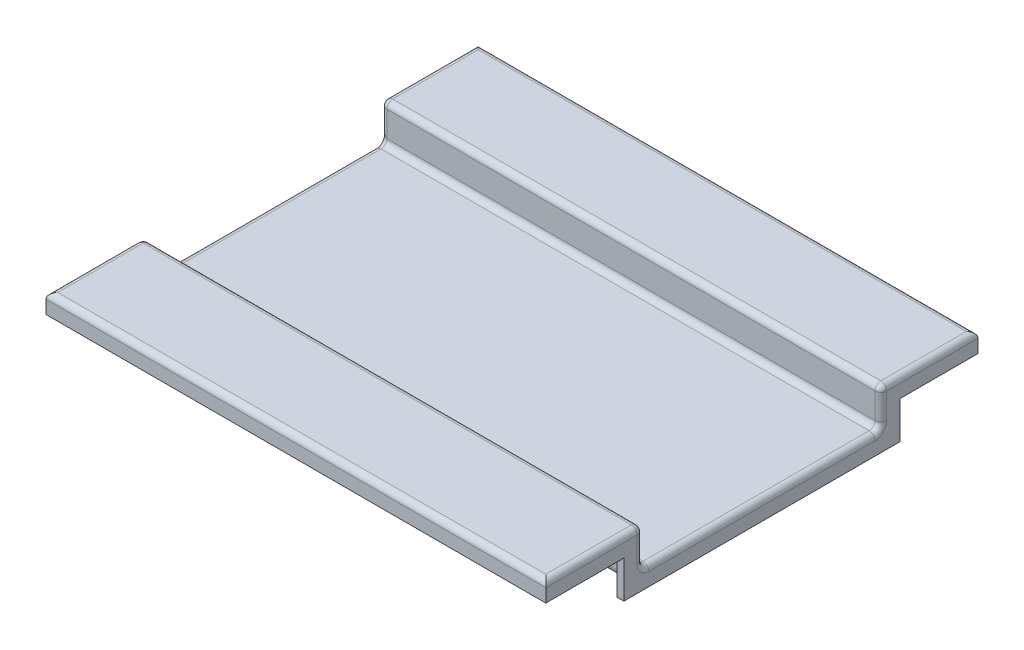
SolidWorks part; units mm, degrees
ref_plane "Alzado" through (0, 0, 0) normal (0, 0, 1) x (1, 0, 0)
ref_plane "Planta" through (0, 0, 0) normal (0, 1, 0) x (1, 0, 0)
ref_plane "Vista lateral" through (0, 0, 0) normal (1, 0, 0) x (0, 0, -1)
sketch "Croquis2" plane through (0, 0, 0) normal (0, 1, 0) x (1, 0, 0)
  line L1 (0, 0) -> (170, 0)
  line L2 (0, 0) -> (0, 147)
  line L3 (0, 147) -> (170, 147)
  line L4 (170, 0) -> (170, 147)
  dimension "D1" = 170
  dimension "D2" = 147
extrude "Saliente-Extruir1" add sketch "Croquis2" along normal blind 19.2
sketch "Croquis5" plane through (0, 19.2, 0) normal (0, 1, 0) x (1, 0, 0)
  line L0 (0, 147) -> (0, 0) construction
  line L1 (0, 33.05) -> (170, 33.05)
  line L2 (0, 33.05) -> (0, 113.95)
  line L3 (0, 113.95) -> (170, 113.95)
  line L4 (170, 33.05) -> (170, 113.95)
  line L5 (170, 0) -> (170, 147) construction
  line L6 (0, 73.5) -> (170, 73.5) construction
  point P10 (0, 73.5)
  dimension "D1" = 80.9
extrude "Cortar-Extruir1" cut sketch "Croquis5" against normal blind 12.7
sketch "Croquis6" plane through (170, 0, 0) normal (1, 0, 0) x (0, 0, -1)
  line L0 (73.5, 0) -> (73.5, 6.5) construction
  line L1 (0, 0) -> (26.55, 0)
  line L2 (0, 0) -> (0, 12.7)
  line L3 (0, 12.7) -> (26.55, 12.7)
  line L4 (26.55, 0) -> (26.55, 12.7)
  line L5 (0, 0) -> (147, 0) construction
  line L6 (33.05, 6.5) -> (113.95, 6.5) construction
  line L7 (0, 19.2) -> (33.05, 19.2) construction
  line L8 (33.05, 6.5) -> (33.05, 19.2) construction
  line L9 (147, 12.7) -> (120.45, 12.7)
  line L10 (120.45, 0) -> (120.45, 12.7)
  line L11 (147, 0) -> (120.45, 0)
  line L12 (147, 0) -> (147, 12.7)
  dimension "D1" = 6.5
  dimension "D2" = 6.5
extrude "Cortar-Extruir2" cut sketch "Croquis6" against normal through all
sketch "Croquis7" plane through (0, 12.7, 0) normal (0, -1, 0) x (1, 0, 0)
  line L0 (0, -73.5) -> (170, -73.5) construction
  line L1 (0, -120.45) -> (0, -26.55) construction
  line L2 (170, -26.55) -> (170, -120.45) construction
  line L3 (85, 0) -> (85, -147) construction
  line L4 (2.3, -120.45) -> (167.7, -120.45)
  line L5 (2.3, -120.45) -> (2.3, -144.7)
  line L6 (2.3, -144.7) -> (167.7, -144.7)
  line L7 (167.7, -120.45) -> (167.7, -144.7)
  line L8 (0, 0) -> (170, 0) construction
  line L9 (0, -147) -> (170, -147) construction
  line L10 (0, -26.55) -> (0, 0) construction
  line L11 (170, -26.55) -> (170, 0) construction
  line L12 (0, -120.45) -> (170, -120.45) construction
  line L13 (2.3, -2.3) -> (167.7, -2.3)
  line L14 (167.7, -26.55) -> (167.7, -2.3)
  line L15 (2.3, -26.55) -> (167.7, -26.55)
  line L16 (2.3, -26.55) -> (2.3, -2.3)
  point P21 (2.3, -2.3)
  dimension "D1" = 2.3
  dimension "D2" = 2.3
  dimension "D3" = 2.3
extrude "Cortar-Extruir4" cut sketch "Croquis7" against normal blind 3
sketch "Croquis8" plane through (0, 0, -26.55) normal (0, 0, 1) x (1, 0, 0)
  line L0 (0, 0) -> (170, 0) construction
  line L1 (2.3, 15.7) -> (167.7, 15.7)
  line L2 (2.3, 15.7) -> (2.3, 0)
  line L3 (2.3, 0) -> (167.7, 0)
  line L4 (167.7, 15.7) -> (167.7, 0)
  point P7 (167.7, 15.7)
extrude "Cortar-Extruir6" cut sketch "Croquis8" against normal blind 3
sketch "Croquis9" plane through (0, 0, -120.45) normal (0, 0, -1) x (-1, 0, 0)
  line L0 (0, 0) -> (-170, 0) construction
  line L1 (-167.7, 15.7) -> (-2.3, 15.7)
  line L2 (-167.7, 15.7) -> (-167.7, 0)
  line L3 (-167.7, 0) -> (-2.3, 0)
  line L4 (-2.3, 15.7) -> (-2.3, 0)
  line L5 (-2.3, 15.7) -> (-2.3, 12.7) construction
  point P7 (-2.3, 15.7)
extrude "Cortar-Extruir7" cut sketch "Croquis9" against normal blind 3
sketch "Croquis10" plane through (0, 0, 0) normal (0, -1, 0) x (1, 0, 0)
  line L1 (2.3, -29.55) -> (167.7, -29.55)
  line L2 (2.3, -29.55) -> (2.3, -117.45)
  line L3 (2.3, -117.45) -> (167.7, -117.45)
  line L4 (167.7, -29.55) -> (167.7, -117.45)
extrude "Cortar-Extruir8" cut sketch "Croquis10" against normal blind 3
sketch "Croquis15" plane through (0, 3, 0) normal (0, -1, 0) x (1, 0, 0)
  line L0 (2.3, -73.5) -> (167.7, -73.5) construction
  line L1 (2.3, -29.55) -> (2.3, -117.45) construction
  line L2 (167.7, -117.45) -> (167.7, -29.55) construction
  line L3 (85, -29.55) -> (85, -117.45) construction
  line L4 (167.7, -29.55) -> (2.3, -29.55) construction
  line L5 (2.3, -117.45) -> (167.7, -117.45) construction
  line L7 (80, -40.7109) -> (90, -40.7109)
  line L8 (80, -40.7109) -> (80, -59.4109)
  line L10 (90, -40.7109) -> (90, -59.4109)
  line L12 (90, -106.2891) -> (90, -87.5891)
  line L13 (80, -106.2891) -> (90, -106.2891)
  line L14 (80, -106.2891) -> (80, -87.5891)
  line L15 (70.9109, -78.5) -> (52.2109, -78.5)
  line L16 (99.0891, -68.5) -> (117.7891, -68.5)
  line L18 (99.0891, -78.5) -> (117.7891, -78.5)
  line L19 (117.7891, -68.5) -> (117.7891, -78.5)
  line L20 (52.2109, -68.5) -> (52.2109, -78.5)
  line L21 (70.9109, -68.5) -> (52.2109, -68.5)
  arc A0 (80, -59.4109) -> (70.9109, -68.5) centre (85, -73.5) ccw
  arc A1 (70.9109, -78.5) -> (80, -87.5891) centre (85, -73.5) ccw
  arc A2 (90, -87.5891) -> (99.0891, -78.5) centre (85, -73.5) ccw
  arc A3 (99.0891, -68.5) -> (90, -59.4109) centre (85, -73.5) ccw
  point P20 (85, -40.7109)
  point P29 (117.7891, -73.5)
  dimension "D1" = 29.9
  dimension "D2" = 18.7
  dimension "D3" = 10
  dimension "D4" = 18.7
  dimension "D5" = 18.7
  dimension "D6" = 18.7
  dimension "D7" = 10
  dimension "D8" = 18.7
  dimension "D9" = 18.7
extrude "Saliente-Extruir4" add sketch "Croquis15" along normal blind 18.7
sketch "Croquis20" plane through (90, 0, 0) normal (1, 0, 0) x (0, 0, -1)
  line L0 (59.4109, -15.7) -> (40.7109, 3)
  line L1 (40.7109, 3) -> (40.7109, -15.7)
  line L2 (40.7109, -15.7) -> (59.4109, -15.7)
extrude "Cortar-Extruir11" cut sketch "Croquis20" against normal up to next
sketch "Croquis21" plane through (90, 0, 0) normal (1, 0, 0) x (0, 0, -1)
  line L0 (87.5891, -15.7) -> (106.2891, 3)
  line L1 (106.2891, 3) -> (106.2891, -15.7)
  line L2 (87.5891, -15.7) -> (106.2891, -15.7)
extrude "Cortar-Extruir13" cut sketch "Croquis21" against normal up to next
sketch "Croquis22" plane through (0, 0, -78.5) normal (0, 0, -1) x (-1, 0, 0)
  line L0 (-99.0891, -15.7) -> (-117.7891, 3)
  line L1 (-117.7891, 3) -> (-117.7891, -15.7)
  line L2 (-117.7891, -15.7) -> (-99.0891, -15.7)
  line L3 (-70.9109, -15.7) -> (-52.2109, -15.7)
  line L4 (-52.2109, -15.7) -> (-52.2109, 3)
  line L5 (-52.2109, 3) -> (-70.9109, -15.7)
extrude "Cortar-Extruir14" cut sketch "Croquis22" against normal up to next
sketch "Croquis23" plane through (0, -15.7, 0) normal (0, -1, 0) x (1, 0, 0)
  line L0 (85, -59.4109) -> (85, -87.5891) construction
  line L1 (80, -59.4109) -> (90, -59.4109) construction
  line L2 (80, -87.5891) -> (90, -87.5891) construction
  line L3 (85, -59.4109) -> (85, -40.7109) construction
  line L4 (90, -40.7109) -> (80, -40.7109) construction
  line L5 (85, -87.5891) -> (85, -106.2891) construction
  line L6 (80, -106.2891) -> (90, -106.2891) construction
  line L7 (52.2109, -73.5) -> (117.7891, -73.5) construction
  line L8 (52.2109, -68.5) -> (52.2109, -78.5) construction
  line L9 (117.7891, -78.5) -> (117.7891, -68.5) construction
  line L10 (70.9109, -68.5) -> (70.9109, -78.5) construction
  line L11 (52.2109, -70.7) -> (70.0691, -70.7)
  line L12 (52.2109, -70.7) -> (52.2109, -76.3)
  line L13 (52.2109, -76.3) -> (70.0691, -76.3)
  line L14 (70.0691, -70.7) -> (70.0691, -76.3)
  line L15 (117.7891, -76.3) -> (99.9309, -76.3)
  line L16 (99.9309, -70.7) -> (99.9309, -76.3)
  line L17 (117.7891, -70.7) -> (99.9309, -70.7)
  line L18 (117.7891, -70.7) -> (117.7891, -76.3)
  line L19 (82.2, -88.4291) -> (87.8, -88.4291)
  line L20 (82.2, -40.7109) -> (87.8, -40.7109)
  line L21 (82.2, -40.7109) -> (82.2, -58.5709)
  line L22 (82.2, -58.5709) -> (87.8, -58.5709)
  line L23 (87.8, -40.7109) -> (87.8, -58.5709)
  line L24 (87.8, -106.2891) -> (87.8, -88.4291)
  line L25 (82.2, -106.2891) -> (87.8, -106.2891)
  line L26 (82.2, -106.2891) -> (82.2, -88.4291)
  circle A0 centre (85, -73.5) radius 12.225
  point P24 (70.0691, -73.5)
  point P35 (85, -58.5709)
  dimension "D1" = 24.45
  dimension "D2" = 0.8419
  dimension "D3" = 5.6
  dimension "D4" = 0.84
  dimension "D5" = 5.6
extrude "Cortar-Extruir15" cut sketch "Croquis23" against normal blind 18.7
fillet "Redondeo1" radius 2 2 edges at (85, 3, -29.55) (85, 3, -117.45)
fillet "Redondeo2" radius 2 2 edges at (85, 6.5, -33.05) (85, 6.5, -113.95)
fillet "Redondeo4" radius 2 2 edges at (85, 19.2, -113.95) (85, 19.2, -33.05)
fillet "Redondeo5" radius 2 2 edges at (85, 15.7, -117.45) (85, 15.7, -29.55)
fillet "Redondeo6" radius 2 20 edges at (170, 18.6142, -114.5358) (170, 12.85, -113.95) (170, 7.0858, -113.3642) (170, 7.0858, -33.6358) (170, 12.85, -33.05) (170, 18.6142, -32.4642) (0, 18.6142, -114.5358) (0, 12.85, -113.95) (0, 7.0858, -113.3642) (0, 7.0858, -33.6358) (0, 12.85, -33.05) (0, 18.6142, -32.4642) (170, 6.5, -73.5) (0, 6.5, -73.5) (170, 19.2, -131.475) (85, 19.2, -147) (0, 19.2, -131.475) (170, 19.2, -15.525) (85, 19.2, 0) (0, 19.2, -15.525)
fillet "Redondeo7" radius 1.1 2 edges at (108.4391, -6.35, -68.5) (108.86, -5.9291, -70.7)
fillet "Redondeo8" radius 1.1 2 edges at (108.86, -5.9291, -76.3) (108.4391, -6.35, -78.5)
fillet "Redondeo9" radius 1.1 4 edges at (80, -6.35, -96.9391) (82.2, -5.93, -97.3591) (87.8, -5.93, -97.3591) (90, -6.35, -96.9391)
fillet "Redondeo10" radius 1.1 8 edges at (90, -6.35, -50.0609) (87.8, -5.93, -49.6409) (82.2, -5.93, -49.6409) (80, -6.35, -50.0609) (61.5609, -6.35, -68.5) (61.14, -5.9291, -70.7) (61.14, -5.9291, -76.3) (61.5609, -6.35, -78.5)
